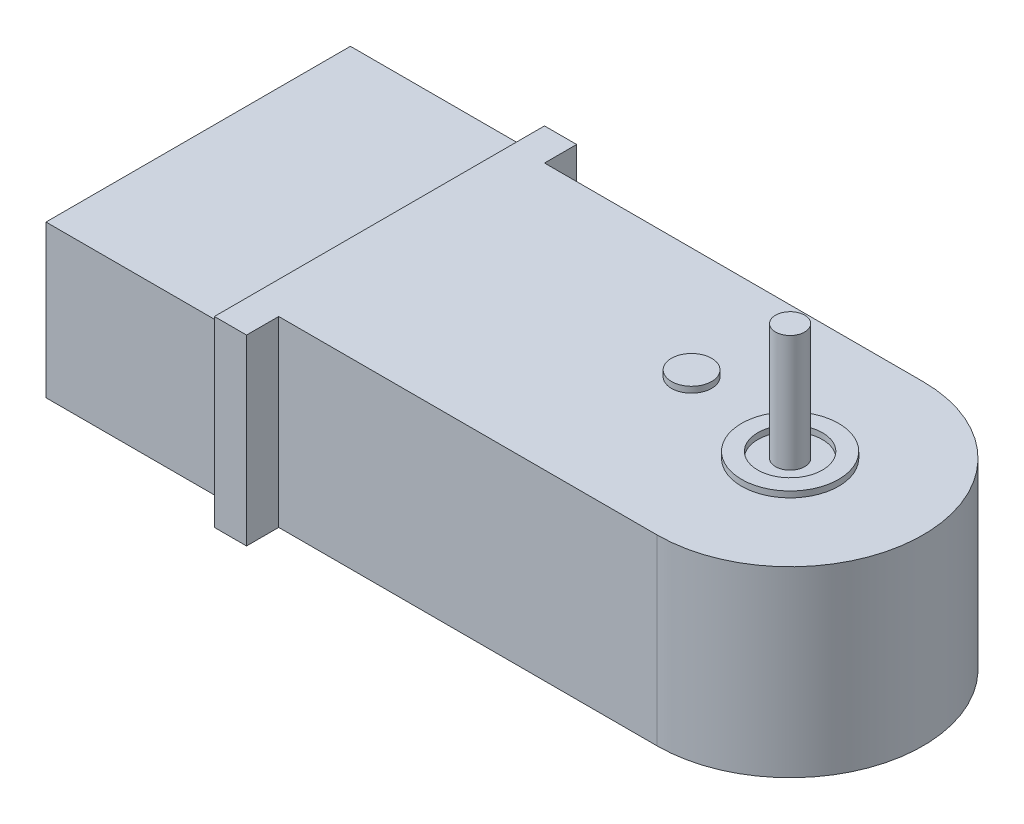
SolidWorks part; units mm, degrees
ref_plane "Front Plane" through (0, 0, 0) normal (0, 0, 1) x (1, 0, 0)
ref_plane "Top Plane" through (0, 0, 0) normal (0, 1, 0) x (1, 0, 0)
ref_plane "Right Plane" through (0, 0, 0) normal (1, 0, 0) x (0, 0, -1)
sketch "Sketch1" plane through (0, 0, 0) normal (0, 1, 0) x (1, 0, 0)
  line L0 (-30.84, 0) -> (0, 0) construction
  line L1 (0, 9.98) -> (-28.425, 9.98)
  line L2 (-28.425, 9.98) -> (-28.425, 12.395)
  line L3 (-28.425, 12.395) -> (-30.84, 12.395)
  line L4 (-30.84, 12.395) -> (-30.84, -12.395)
  line L5 (-30.84, -12.395) -> (-28.425, -12.395)
  line L6 (-28.425, -12.395) -> (-28.425, -9.98)
  line L7 (-28.425, -9.98) -> (0, -9.98)
  arc A0 (0, -9.98) -> (0, 9.98) centre (0, 0) ccw
  dimension "D1" = 19.96
  dimension "D2" = 30.84
  dimension "D3" = 24.79
extrude "Gear Box" add sketch "Sketch1" along normal blind 6.86 and the other way blind 6.86
sketch "Sketch2" plane through (0, 0, 0) normal (0, 1, 0) x (1, 0, 0)
  line L0 (0, 0) -> (-44.45, 0) construction
  line L1 (-30.84, 11.43) -> (-44.45, 11.43)
  line L2 (-30.84, 11.43) -> (-30.84, -11.43)
  line L3 (-30.84, -11.43) -> (-44.45, -11.43)
  line L4 (-44.45, 11.43) -> (-44.45, -11.43)
  line L5 (-30.84, 12.395) -> (-30.84, -12.395) construction
  dimension "D1" = 22.86
  dimension "D2" = 13.61
extrude "Motor" add sketch "Sketch2" along normal blind 5.715 and the other way blind 5.715
sketch "Sketch3" plane through (0, 6.86, 0) normal (0, 1, 0) x (1, 0, 0)
  line L0 (-30.84, 12.395) -> (-30.84, -12.395) construction
  line L1 (-28.425, -9.98) -> (0, -9.98) construction
  circle A0 centre (-9, 1.6) radius 1.51
  circle A1 centre (0, 0) radius 3.645
  circle A2 centre (0, 0) radius 2.43
  dimension "D1" = 3.02
  dimension "D4" = 7.29
  dimension "D5" = 4.86
  dimension "D2" = 21.84
  dimension "D3" = 11.58
extrude "Spacer" add sketch "Sketch3" along normal blind 0.45
sketch "Sketch5" plane through (0, -6.86, 0) normal (0, -1, 0) x (1, 0, 0)
  circle A0 centre (0, 0) radius 3.645
  circle A1 centre (0, 0) radius 2.43
  circle A2 centre (0, 0) radius 3.645 construction
  circle A3 centre (0, 0) radius 2.43 construction
extrude "Spacer(back)" add sketch "Sketch5" along normal blind 0.45
sketch "Sketch4" plane through (0, 6.86, 0) normal (0, 1, 0) x (1, 0, 0)
  circle A0 centre (0, 0) radius 1.095
  dimension "D1" = 2.19
extrude "Output Shaft" add sketch "Sketch4" along normal blind 8.76
